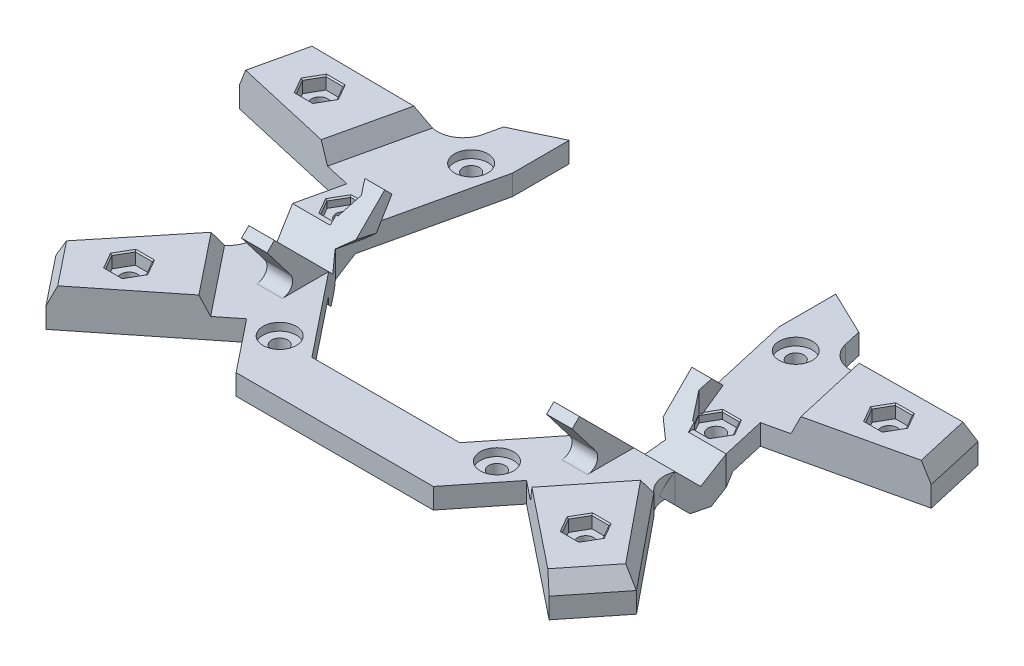
SolidWorks part; units mm, degrees
note: The reader was unsure of these and kept them because the rebuilt part matched: shared geometry of "Sketch20<3>", "Sketch20<4>", "Sketch20<5>", "Sketch20<6>", "Sketch20<8>", "Sketch20<9>", "Sketch22<2>".
ref_plane "Front Plane" through (0, 0, 0) normal (0, 0, 1) x (1, 0, 0)
ref_plane "Top Plane" through (0, 0, 0) normal (0, 1, 0) x (1, 0, 0)
ref_plane "Right Plane" through (0, 0, 0) normal (1, 0, 0) x (0, 0, -1)
sketch "Sketch2" plane through (0, 0, 0) normal (0, 1, 0) x (1, 0, 0)
  line L0 (0, 0) -> (-66.1879, 15.1069) construction
  line L1 (0, 0) -> (66.1879, 15.1069) construction
  line L2 (0, 0) -> (-53.0785, -42.3287) construction
  line L3 (-53.457, -34.5725) -> (-35.2012, -20.0141)
  line L4 (37.5952, 15.0429) -> (40.399, 2.7588)
  line L5 (40.399, 2.7588) -> (63.1636, 7.9547)
  line L6 (63.1636, 7.9547) -> (60.3598, 20.2387)
  line L7 (35.4724, 24.3437) -> (34.7107, 27.6809)
  line L8 (34.7107, 27.6809) -> (0, 44.3967)
  line L9 (0, 44.3967) -> (-34.7107, 27.6809)
  line L10 (-34.7107, 27.6809) -> (-43.2835, -9.8792)
  line L11 (41.1493, -12.5554) -> (43.2835, -9.8792)
  line L12 (-19.263, -40) -> (19.263, -40)
  line L13 (0, 0) -> (53.0785, -42.3287) construction
  line L14 (60.3598, 20.2387) -> (37.5952, 15.0429)
  line L15 (53.457, -34.5725) -> (35.2012, -20.0141)
  line L16 (53.457, -34.5725) -> (45.601, -44.4236)
  line L17 (45.601, -44.4236) -> (27.3453, -29.8651)
  line L18 (49.1506, -47.2543) -> (56.7197, -37.7628)
  line L19 (0, 44.3967) -> (0, -40) construction
  line L20 (-63.1636, 7.9547) -> (-60.3598, 20.2387)
  line L21 (-60.3598, 20.2387) -> (-37.5952, 15.0429)
  line L22 (-37.5952, 15.0429) -> (-40.399, 2.7588)
  line L23 (-40.399, 2.7588) -> (-63.1636, 7.9547)
  line L24 (45.601, -44.4236) -> (49.1506, -47.2543)
  line L25 (55.928, -30.7362) -> (41.941, -19.582)
  line L26 (19.263, -40) -> (27.3453, -29.8651)
  line L27 (35.2012, -20.0141) -> (27.3453, -29.8651)
  line L28 (58.9011, 24.5626) -> (41.4596, 20.5817)
  line L29 (35.4724, 24.3437) -> (43.2835, -9.8792)
  line L30 (63.1636, 7.9547) -> (67.5897, 8.9649)
  line L31 (67.5897, 8.9649) -> (64.8883, 20.8005)
  line L32 (-63.1636, 7.9547) -> (-67.5897, 8.9649)
  line L33 (34.7107, 27.6809) -> (34.7052, 27.7315)
  line L34 (-67.5897, 8.9649) -> (-64.8883, 20.8005)
  line L35 (-58.9011, 24.5626) -> (-41.4596, 20.5817)
  line L36 (0, 0) -> (17.3553, 36.0388) construction
  line L37 (0, 0) -> (-17.3553, 36.0388) construction
  line L38 (35.2012, -20.0141) -> (41.1493, -12.5554)
  line L39 (-53.457, -34.5725) -> (-45.601, -44.4236)
  line L40 (-45.601, -44.4236) -> (-49.1506, -47.2543)
  line L41 (-43.2835, -9.8792) -> (-19.263, -40) construction
  line L42 (-49.1506, -47.2543) -> (-56.7197, -37.7628)
  line L43 (-55.928, -30.7362) -> (-41.941, -19.582)
  line L44 (-43.2835, -9.8792) -> (-41.1493, -12.5554)
  line L45 (-19.263, -40) -> (-35.2012, -20.0141)
  line L46 (-35.2012, -20.0141) -> (-41.1493, -12.5554)
  line L47 (19.263, -40) -> (27.3453, -29.8651) [skipped]
  line L48 (-45.601, -44.4236) -> (-27.3453, -29.8651)
  line L49 (-64.8883, 20.8005) -> (-41.4596, 20.5817)
  line L50 (-67.5897, 8.9649) -> (-41.8371, -3.5422)
  line L51 (-56.7197, -37.7628) -> (-41.941, -19.582)
  line L52 (-49.1506, -47.2543) -> (-23.3157, -34.9181)
  line L53 (56.7197, -37.7628) -> (41.941, -19.582)
  line L54 (64.8883, 20.8005) -> (41.4596, 20.5817)
  line L55 (49.1506, -47.2543) -> (23.3157, -34.9181)
  line L56 (67.5897, 8.9649) -> (41.8371, -3.5422)
  circle A0 centre (63.9065, 14.5862) radius 1
  circle A1 centre (0, 0) radius 40 construction
  circle A2 centre (36.8523, 8.4113) radius 1
  circle A3 centre (-63.9065, 14.5862) radius 1
  circle A4 centre (-36.8523, 8.4113) radius 1
  circle A5 centre (51.2491, -40.8698) radius 1
  circle A6 centre (29.5532, -23.5679) radius 1
  arc A7 (56.7197, -37.7628) -> (55.928, -30.7362) centre (52.8106, -34.6454) ccw
  arc A8 (41.941, -19.582) -> (41.1493, -12.5554) centre (45.0585, -15.6728) cw
  arc A9 (58.9011, 24.5626) -> (64.8883, 20.8005) centre (60.0137, 19.6879) cw
  arc A10 (35.4724, 24.3437) -> (41.4596, 20.5817) centre (40.347, 25.4563) ccw
  arc A11 (-58.9011, 24.5626) -> (-64.8883, 20.8005) centre (-60.0137, 19.6879) ccw
  arc A12 (-35.4724, 24.3437) -> (-41.4596, 20.5817) centre (-40.347, 25.4563) cw
  circle A13 centre (-29.5532, -23.5679) radius 1
  circle A14 centre (-51.2491, -40.8698) radius 1
  arc A15 (-56.7197, -37.7628) -> (-55.928, -30.7362) centre (-52.8106, -34.6454) cw
  arc A16 (-41.941, -19.582) -> (-41.1493, -12.5554) centre (-45.0585, -15.6728) ccw
  dimension "D1" = 80
  dimension "D4" = 2
  dimension "D12" = 5
  dimension "D13" = 23.35
  dimension "D15" = 2
  dimension "D20" = 5
  dimension "D7" = 5
  dimension "D22" = 5
  dimension "D23" = 5
  dimension "D24" = 5
  dimension "D25" = 6.5
  dimension "D2" = 12.6
  dimension "D3" = 23.35
  dimension "D5" = 2.2
  dimension "D6" = 2.2
  dimension "D8" = 38.526
  dimension "D9" = 4.54
  dimension "D10" = 12.6
  dimension "D11" = 4.54
  dimension "D14" = 38.526
  dimension "D16" = 2.2
  dimension "D17" = 4.54
  dimension "D18" = 4.54
  dimension "D19" = 2.2
  dimension "D21" = 3.423
  dimension "D26" = 6.5
extrude "Extrude_Base" add sketch "Sketch2" along normal blind 4
sketch "Sketch16" plane through (0, 4, 0) normal (0, 1, 0) x (1, 0, 0)
  line L0 (0, 0) -> (-66.1879, 15.1069) construction
  line L1 (0, 0) -> (66.1879, 15.1069) construction
  line L2 (0, 0) -> (53.0785, -42.3287) construction
  line L3 (0, 0) -> (-53.0785, -42.3287) construction
  line L5 (-67.5897, 8.9649) -> (-64.8883, 20.8005) construction
  line L6 (-49.1506, -47.2543) -> (-56.7197, -37.7628) construction
  line L7 (49.1506, -47.2543) -> (56.7197, -37.7628) construction
  line L8 (67.5897, 8.9649) -> (64.8883, 20.8005) construction
  line L10 (-40.399, 2.7588) -> (-67.5897, 8.9649) construction
  line L11 (40.399, 2.7588) -> (67.5897, 8.9649) construction
  line L12 (49.1506, -47.2543) -> (27.3453, -29.8651) construction
  line L13 (-49.1506, -47.2543) -> (-27.3453, -29.8651) construction
  line L14 (-63.1636, 7.9547) -> (-61.7617, 14.0967) construction
  line L15 (-49.529, -39.4981) -> (-45.601, -44.4236) construction
  line L16 (49.529, -39.4981) -> (45.601, -44.4236) construction
  line L17 (61.7617, 14.0967) -> (63.1636, 7.9547) construction
  circle A0 centre (-55.6196, 12.6948) radius 1.6
  circle A1 centre (55.6196, 12.6948) radius 1.6
  circle A2 centre (44.6035, -35.5701) radius 1.6
  circle A3 centre (-44.6035, -35.5701) radius 1.6
  dimension "D1" = 3.2
  dimension "D2" = 4.54
  dimension "D3" = 6.3
  dimension "D4" = 4.54
  dimension "D5" = 4.54
  dimension "D6" = 4.54
  dimension "D7" = 6.3
  dimension "D8" = 6.3
  dimension "D9" = 6.3
extrude "Cut-Extrude7" cut sketch "Sketch16" against normal through all
sketch "Sketch17" plane through (0, 0, 0) normal (0, -1, 0) x (1, 0, 0)
  circle A0 centre (-44.6035, 35.5701) radius 2.85
  circle A1 centre (55.6196, -12.6948) radius 2.85
  circle A2 centre (44.6035, 35.5701) radius 2.85
  circle A3 centre (-55.6196, -12.6948) radius 2.85
  dimension "D1" = 5.7
extrude "Cut-Extrude8" cut sketch "Sketch17" against normal blind 3
sketch "Sketch18" plane through (0, 4, 0) normal (0, 1, 0) x (1, 0, 0)
  line L0 (-19.263, -40) -> (19.263, -40) construction
  line L1 (14.4472, -30) -> (32.4627, -7.4094)
  line L2 (32.4627, -7.4094) -> (26.033, 20.7606)
  line L3 (26.033, 20.7606) -> (0, 33.2975)
  line L4 (0, 33.2975) -> (-26.033, 20.7606)
  line L5 (-26.033, 20.7606) -> (-32.4627, -7.4094)
  line L6 (-32.4627, -7.4094) -> (-14.4472, -30)
  line L7 (-14.4472, -30) -> (14.4472, -30)
  circle A0 centre (0, 0) radius 30 construction
  dimension "D1" = 10
extrude "Cut-Extrude9" cut sketch "Sketch18" against normal through all
sketch "Sketch19" plane through (0, 4, 0) normal (0, 1, 0) x (1, 0, 0)
  line L0 (0, 0) -> (0, 44.3967) construction
  line L2 (26.033, 0) -> (-26.033, 0)
  line L3 (26.033, 0) -> (26.033, 44.3967)
  line L4 (26.033, 44.3967) -> (-26.033, 44.3967)
  line L5 (-26.033, 0) -> (-26.033, 44.3967)
extrude "Cut-Extrude10" cut sketch "Sketch19" against normal through all
sketch "Sketch20" plane through (0, 0, 0) normal (1, 0, 0) x (0, 0, -1)
  line L0 (-2.8551, 7.0241) -> (-9.8792, 0)
  line L1 (-19.582, 0) -> (-12.5554, 0) construction
  line L2 (-9.8792, 0) -> (-27.4056, 0) construction
  line L3 (-16.7076, 1.1716) -> (-27.3142, 11.7782) construction
  line L4 (-9.8792, 0) -> (-9.8792, -2.6863) construction
  line L5 (-16.9032, 7.0241) -> (-9.8792, 0)
  line L6 (-2.8551, 7.0241) -> (-16.9032, 7.0241)
  line L7 (-5.8792, 4) -> (-3.0508, 1.1716)
  line L8 (2.7588, 4) -> (-9.8792, 4) construction
  line L9 (-3.0508, 1.1716) -> (-8.2223, -4)
  line L10 (-8.2223, -4) -> (-11.536, -4)
  line L11 (-11.536, -4) -> (-16.7076, 1.1716)
  line L12 (-16.7076, 1.1716) -> (-13.8792, 4)
  line L13 (-12.5554, 4) -> (-19.582, 4) construction
  line L14 (-37.7628, 0) -> (-19.582, 0) construction
  line L15 (-27.3142, 11.7782) -> (-24.4858, 14.6066) construction
  line L16 (-24.4858, 14.6066) -> (-16.9032, 7.0241)
  line L17 (-16.7076, 1.1716) -> (-25.9, 13.1924)
  line L18 (-25.9, 13.1924) -> (-24.4858, 14.6066)
  line L19 (-5.8792, 4) -> (-1.3537, 4)
  line L20 (2.7588, 4) -> (-9.8792, 4) construction
  line L21 (-3.0508, 1.1716) -> (-0.2223, 4) construction
  line L22 (-2.8551, 7.0241) -> (-0.2223, 9.6569)
  line L23 (-0.2223, 9.6569) -> (2.6061, 6.8284) construction
  line L24 (2.6061, 6.8284) -> (-0.2223, 4) construction
  line L25 (1.1919, 8.2426) -> (-1.3537, 4)
  line L26 (-0.2223, 9.6569) -> (1.1919, 8.2426)
  line L27 (-1.3537, 4) -> (-3.0508, 1.1716) construction
  line L28 (-1.3537, 4) -> (-0.2223, 4) construction
  dimension "D1" = 45
  dimension "D2" = 4
  dimension "D3" = 4
  dimension "D4" = 15
  dimension "D5" = 8
extrude "Cut-Extrude11" cut sketch "Sketch20" against normal mid plane 90 contours L0 L6 L5
extrude "Boss-Extrude1" add sketch "Sketch20<3>" against normal up to vertex from vertex contours L12 L11 L10 L9 L7 L0 L5
sketch "Sketch20<3>" plane through (0, 0, 0) normal (1, 0, 0) x (0, 0, -1) same geometry as "Sketch20"
extrude "Boss-Extrude2" add sketch "Sketch20<4>" against normal up to vertex from vertex contours L12 L11 L10 L9 L7 L0 L5
sketch "Sketch20<4>" plane through (0, 0, 0) normal (1, 0, 0) x (0, 0, -1) same geometry as "Sketch20"
sketch "Sketch21" plane through (0, 4, 0) normal (0, 1, 0) x (1, 0, 0)
  line L0 (-40.3913, -13.8792) -> (-42.3706, -5.8792)
  line L1 (14.4472, -30) -> (32.4627, -7.4094)
  line L2 (32.4627, -7.4094) -> (26.033, 20.7606)
  line L3 (26.033, 20.7606) -> (0, 33.2975)
  line L4 (0, 33.2975) -> (-26.033, 20.7606)
  line L5 (-26.033, 20.7606) -> (-32.4627, -7.4094)
  line L6 (-32.4627, -7.4094) -> (-14.4472, -30)
  line L7 (-14.4472, -30) -> (14.4472, -30)
  line L8 (-42.3706, -5.8792) -> (-40.399, 2.7588)
  line L9 (-40.399, 2.7588) -> (-45.6046, 3.9469)
  line L10 (-40.399, 2.7588) -> (-67.5897, 8.9649) construction
  line L11 (-45.6046, 3.9469) -> (-47.8474, -5.8792)
  line L12 (-47.8474, -5.8792) -> (-44.0425, -21.2579)
  line L14 (-41.941, -19.582) -> (-43.641, -21.6732)
  line L15 (0, 0) -> (0, -30) construction
  line L16 (44.0425, -21.2579) -> (41.941, -19.582)
  line L17 (47.8474, -5.8792) -> (44.0425, -21.2579)
  line L18 (45.6046, 3.9469) -> (47.8474, -5.8792)
  line L19 (40.399, 2.7588) -> (45.6046, 3.9469)
  line L20 (42.3706, -5.8792) -> (40.399, 2.7588)
  line L21 (40.3913, -13.8792) -> (42.3706, -5.8792)
  line L22 (-56.7197, -37.7628) -> (-41.941, -19.582) construction
  line L23 (-43.641, -21.6732) -> (-44.0425, -21.2579)
  line L24 (-44.0425, -21.2579) -> (-44.0604, -21.2653)
  circle A0 centre (0, 0) radius 30 construction
  arc A2 (-41.941, -19.582) -> (-40.3913, -13.8792) centre (-45.0585, -15.6728) ccw construction
  arc A3 (-40.1667, -16.7076) -> (-40.3913, -13.8792) centre (-45.0585, -15.6728) ccw construction
  spline S0 degree 3 poles (-41.941, -19.582) (-40.2129, -18.2398) (-39.6191, -15.8478) (-40.3913, -13.8792) knots 0 0 0 0 1 1 1 1
  spline S1 degree 2 poles (41.941, -19.582) (39.3008, -17.2375) (40.3913, -13.8792) knots 0 0 0 1 1 1
  arc M9 (-40.3913, -13.8792) -> (-41.941, -19.582) centre (-45.0585, -15.6728) cw
  line M23 (27.3032, -13.8792) -> (14.4472, -30)
  line M24 (14.4472, -30) -> (-14.4472, -30)
  line M25 (-14.4472, -30) -> (-27.3032, -13.8792)
  line M47 (-41.941, -19.582) -> (-56.7197, -37.7628)
extrude "Cut-Extrude12" cut sketch "Sketch21" against normal through all contours S0 L0 L8 L9 L11 L12 L23 M9 M47 | L5 L6 L1 L2 L3 L4 M25 M24 M23 | S1 L16 L17 L18 L19 L20 L21
sketch "Sketch15" plane through (0, 4, 0) normal (0, 1, 0) x (1, 0, 0)
  line L0 (-19.263, -40) -> (19.263, -40) construction
  line L1 (16.8551, -35) -> (37.8731, -8.6443)
  line L2 (37.8731, -8.6443) -> (30.3719, 24.2208)
  line L3 (30.3719, 24.2208) -> (0, 38.8471)
  line L4 (0, 38.8471) -> (-30.3719, 24.2208)
  line L5 (-30.3719, 24.2208) -> (-37.8731, -8.6443)
  line L6 (-37.8731, -8.6443) -> (-16.8551, -35)
  line L7 (-16.8551, -35) -> (16.8551, -35)
  line L8 (0, 0) -> (0, -35) construction
  circle A0 centre (0, 0) radius 35 construction
  circle A1 centre (-31.707, 18.3712) radius 1.6
  circle A2 centre (31.707, 18.3712) radius 1.6
  circle A3 centre (21.2195, -29.5272) radius 1.6
  circle A4 centre (36.3154, -1.8198) radius 1.6
  circle A7 centre (-21.2195, -29.5272) radius 1.6
  circle A8 centre (-36.3154, -1.8198) radius 1.6
  dimension "D5" = 3.2
  dimension "D1" = 5
  dimension "D2" = 33.7102
  dimension "D3" = 6
  dimension "D4" = 6
  dimension "D6" = 7
  dimension "D7" = 7
extrude "Cut-Extrude6" cut sketch "Sketch15" against normal through all contours L5 A1 | L5 A1 | L5 A8 | A4 L2 | A4 L2 | L2 A2 | L2 A2 | L6 A7 | L6 A7 | A3 L1 | A3 L1
sketch "Sketch22" plane through (0, 4, 0) normal (0, 1, 0) x (1, 0, 0)
  line L1 (-34.6411, -4.7198) -> (-32.9668, -1.8198)
  line L2 (-32.9668, -1.8198) -> (-34.6411, 1.0802)
  line L3 (-34.6411, 1.0802) -> (-37.9898, 1.0802)
  line L4 (-37.9898, 1.0802) -> (-39.6641, -1.8198)
  line L5 (-39.6641, -1.8198) -> (-37.9898, -4.7198)
  line L6 (-37.9898, -4.7198) -> (-34.6411, -4.7198)
  line L7 (37.9898, -4.7198) -> (39.6641, -1.8198)
  line L8 (39.6641, -1.8198) -> (37.9898, 1.0802)
  line L9 (37.9898, 1.0802) -> (34.6411, 1.0802)
  line L10 (34.6411, 1.0802) -> (32.9668, -1.8198)
  line L11 (32.9668, -1.8198) -> (34.6411, -4.7198)
  line L12 (34.6411, -4.7198) -> (37.9898, -4.7198)
  circle A0 centre (-36.3154, -1.8198) radius 2.9 construction
  circle A1 centre (36.3154, -1.8198) radius 2.9 construction
  dimension "D1" = 5.8
extrude "Cut-Extrude13" cut sketch "Sketch22" against normal blind 1.5
sketch "Sketch24" plane through (0, 4, 0) normal (0, 1, 0) x (1, 0, 0)
  line L0 (-67.5897, 8.9649) -> (-64.8883, 20.8005)
  line L1 (-64.8883, 20.8005) -> (-41.4596, 20.5817)
  line L2 (-41.4596, 20.5817) -> (-45.2736, 3.8714)
  line L3 (-40.399, 2.7588) -> (-67.5897, 8.9649) construction
  line L4 (-45.2736, 3.8714) -> (-67.5897, 8.9649)
  line L5 (-56.7197, -37.7628) -> (-41.941, -19.582)
  line L6 (-41.941, -19.582) -> (-31.2544, -32.9826)
  line L7 (-49.1506, -47.2543) -> (-27.3453, -29.8651) construction
  line L8 (-31.2544, -32.9826) -> (-49.1506, -47.2543)
  line L9 (-49.1506, -47.2543) -> (-56.7197, -37.7628)
  line L10 (0, 0) -> (0, -30) construction
  line L11 (-14.4472, -30) -> (14.4472, -30) construction
  line L12 (49.1506, -47.2543) -> (56.7197, -37.7628)
  line L13 (31.2544, -32.9826) -> (49.1506, -47.2543)
  line L14 (41.941, -19.582) -> (31.2544, -32.9826)
  line L15 (56.7197, -37.7628) -> (41.941, -19.582)
  line L16 (45.2736, 3.8714) -> (67.5897, 8.9649)
  line L17 (41.4596, 20.5817) -> (45.2736, 3.8714)
  line L18 (64.8883, 20.8005) -> (41.4596, 20.5817)
  line L19 (67.5897, 8.9649) -> (64.8883, 20.8005)
extrude "Boss-Extrude3" add sketch "Sketch24" along normal blind 3.5
sketch "Sketch25" plane through (0, 0, 0) normal (0, -1, 0) x (1, 0, 0)
  circle A0 centre (-44.6035, 35.5701) radius 1.6
  circle A1 centre (44.6035, 35.5701) radius 1.6
  circle A2 centre (55.6196, -12.6948) radius 1.6
  circle A3 centre (-55.6196, -12.6948) radius 1.6
extrude "Cut-Extrude14" cut sketch "Sketch25" against normal up to vertex (7.5 mm away) up to point (-64.8883, 7.5, -20.8005)
sketch "Sketch26" plane through (0, 7.5, 0) normal (0, 1, 0) x (1, 0, 0)
  line L1 (53.9453, 15.5948) -> (52.271, 12.6948)
  line L2 (52.271, 12.6948) -> (53.9453, 9.7948)
  line L3 (53.9453, 9.7948) -> (57.294, 9.7948)
  line L4 (57.294, 9.7948) -> (58.9683, 12.6948)
  line L5 (58.9683, 12.6948) -> (57.294, 15.5948)
  line L6 (57.294, 15.5948) -> (53.9453, 15.5948)
  line L7 (42.9292, -32.6701) -> (41.2549, -35.5701)
  line L8 (41.2549, -35.5701) -> (42.9292, -38.4701)
  line L9 (42.9292, -38.4701) -> (46.2778, -38.4701)
  line L10 (46.2778, -38.4701) -> (47.9521, -35.5701)
  line L11 (47.9521, -35.5701) -> (46.2778, -32.6701)
  line L12 (46.2778, -32.6701) -> (42.9292, -32.6701)
  line L13 (-42.9292, -38.4701) -> (-41.2549, -35.5701)
  line L14 (-41.2549, -35.5701) -> (-42.9292, -32.6701)
  line L15 (-42.9292, -32.6701) -> (-46.2778, -32.6701)
  line L16 (-46.2778, -32.6701) -> (-47.9521, -35.5701)
  line L17 (-47.9521, -35.5701) -> (-46.2778, -38.4701)
  line L18 (-46.2778, -38.4701) -> (-42.9292, -38.4701)
  line L19 (-57.294, 15.5948) -> (-58.9683, 12.6948)
  line L20 (-58.9683, 12.6948) -> (-57.294, 9.7948)
  line L21 (-57.294, 9.7948) -> (-53.9453, 9.7948)
  line L22 (-53.9453, 9.7948) -> (-52.271, 12.6948)
  line L23 (-52.271, 12.6948) -> (-53.9453, 15.5948)
  line L24 (-53.9453, 15.5948) -> (-57.294, 15.5948)
  circle A0 centre (55.6196, 12.6948) radius 2.9 construction
  circle A1 centre (44.6035, -35.5701) radius 2.9 construction
  circle A2 centre (-44.6035, -35.5701) radius 2.9 construction
  circle A3 centre (-55.6196, 12.6948) radius 2.9 construction
  dimension "D1" = 5.8
extrude "Cut-Extrude15" cut sketch "Sketch26" against normal blind 2.5
chamfer "Chamfer1" distance 3.5 angle 25 13 edges at (40.2025, 7.5, 40.1184) (52.9351, 7.5, 42.5085) (49.3304, 7.5, 28.6724) (36.5977, 7.5, 26.2823) (-52.9351, 7.5, 42.5085) (-49.3304, 7.5, 28.6724) (-36.5977, 7.5, 26.2823) (-66.239, 7.5, -14.8827) (-53.174, 7.5, -20.6911) (-43.3666, 7.5, -12.2265) (43.3666, 7.5, -12.2265) (66.239, 7.5, -14.8827) (53.174, 7.5, -20.6911)
chamfer "Chamfer2" distance 0.25 angle 45 36 edges at (-47.115, 7.5, 37.0201) (-44.6035, 7.5, 38.4701) (-42.092, 7.5, 37.0201) (-42.092, 7.5, 34.1201) (-47.115, 7.5, 34.1201) (-44.6035, 7.5, 32.6701) (42.092, 7.5, 34.1201) (42.092, 7.5, 37.0201) (44.6035, 7.5, 38.4701) (47.115, 7.5, 37.0201) (47.115, 7.5, 34.1201) (44.6035, 7.5, 32.6701) (53.1082, 7.5, -11.2448) (55.6196, 7.5, -9.7948) (58.1311, 7.5, -11.2448) (58.1311, 7.5, -14.1448) (55.6196, 7.5, -15.5948) (53.1082, 7.5, -14.1448) (38.8269, 4, 3.2698) (36.3154, 4, 4.7198) (33.804, 4, 3.2698) (33.804, 4, 0.3698) (38.8269, 4, 0.3698) (36.3154, 4, -1.0802) (-58.1311, 7.5, -14.1448) (-58.1311, 7.5, -11.2448) (-55.6196, 7.5, -9.7948) (-53.1082, 7.5, -11.2448) (-53.1082, 7.5, -14.1448) (-55.6196, 7.5, -15.5948) (-33.804, 4, 3.2698) (-36.3154, 4, 4.7198) (-38.8269, 4, 3.2698) (-38.8269, 4, 0.3698) (-36.3154, 4, -1.0802) (-33.804, 4, 0.3698)
sketch "Sketch27" plane through (0, 4, 0) normal (0, 1, 0) x (1, 0, 0)
  circle A0 centre (-31.707, 18.3712) radius 3.25
  circle A1 centre (31.707, 18.3712) radius 3.25
  circle A2 centre (-21.2195, -29.5272) radius 3.25
  circle A3 centre (21.2195, -29.5272) radius 3.25
  dimension "D1" = 6.5
extrude "Cut-Extrude16" cut sketch "Sketch27" against normal blind 1.5
extrude "Boss-Extrude4" add sketch "Sketch20<5>" along normal blind 5 from vertex at 27.3032 contours L18 L17 L12 L5 L16
sketch "Sketch20<5>" plane through (0, 0, 0) normal (1, 0, 0) x (0, 0, -1) same geometry as "Sketch20"
extrude "Boss-Extrude5" add sketch "Sketch20<6>" against normal blind 5 from vertex at -27.3032 contours L18 L17 L12 L5 L16
sketch "Sketch20<6>" plane through (0, 0, 0) normal (1, 0, 0) x (0, 0, -1) same geometry as "Sketch20"
fillet "Fillet1" radius 2 2 edges at (29.8032, 4, 18.8705) (-29.8032, 4, 18.8705)
extrude "Boss-Extrude6" add sketch "Sketch20<8>" along normal blind 5 from offset 30 contours L26 L22 L0 L19 L25
sketch "Sketch20<8>" plane through (0, 0, 0) normal (1, 0, 0) x (0, 0, -1) same geometry as "Sketch20"
extrude "Boss-Extrude7" add sketch "Sketch20<9>" against normal blind 5 from offset 30 contours L26 L22 L0 L19 L25 offset against normal yes
sketch "Sketch20<9>" plane through (0, 0, 0) normal (1, 0, 0) x (0, 0, -1) same geometry as "Sketch20"
extrude "Cut-Extrude17" cut sketch "Sketch22<2>" along normal blind 15
sketch "Sketch22<2>" plane through (0, 4, 0) normal (0, 1, 0) x (1, 0, 0) same geometry as "Sketch22"
chamfer "Chamfer3" distance 2 angle 45 2 edges at (31.5969, 4, 3.6164) (-31.5969, 4, 3.6164)
sketch "Sketch28" plane through (0, 4, 0) normal (0, 1, 0) x (1, 0, 0)
  line L1 (34.6411, 1.0802) -> (37.9898, 1.0802)
  line L2 (34.6411, 1.0802) -> (34.6411, 1.8218)
  line L3 (34.6411, 1.8218) -> (37.9898, 1.8218)
  line L4 (37.9898, 1.0802) -> (37.9898, 1.8218)
  line L5 (-34.6411, 1.0802) -> (-37.9921, 1.0802)
  line L6 (-34.6411, 1.0802) -> (-34.6411, 2.2534)
  line L7 (-34.6411, 2.2534) -> (-37.9921, 2.2534)
  line L8 (-37.9921, 1.0802) -> (-37.9921, 2.2534)
extrude "Cut-Extrude18" cut sketch "Sketch28" along normal blind 5
